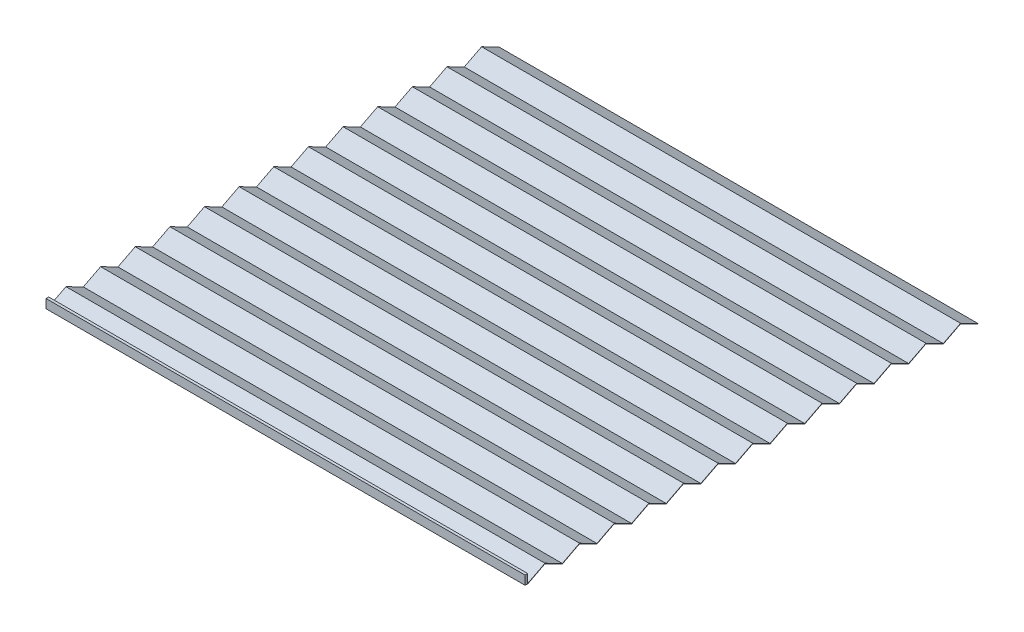
SolidWorks part; units mm, degrees
ref_plane "Front Plane" through (0, 0, 0) normal (0, 0, 1) x (1, 0, 0)
ref_plane "Top Plane" through (0, 0, 0) normal (0, 1, 0) x (1, 0, 0)
ref_plane "Right Plane" through (0, 0, 0) normal (1, 0, 0) x (0, 0, -1)
sketch "Sketch2" plane through (0, 0, 0) normal (0, 0, 1) x (1, 0, 0)
  line L1 (-270, 10) -> (270, 10)
  line L2 (-270, 10) -> (-270, 0)
  line L3 (-270, 0) -> (270, 0)
  line L4 (270, 10) -> (270, 0)
  point P4 (0, 0)
  dimension "D1" = 10
  dimension "D2" = 540
extrude "Boss-Extrude1" add sketch "Sketch2" along normal blind 3
sketch "Sketch3" plane through (270, 0, 0) normal (1, 0, 0) x (0, 0, -1)
  line L0 (0, 10) -> (507.5563, 10) construction
  line L1 (0, 0) -> (507.5563, 0) construction
  line L2 (507.5563, 10) -> (507.5563, 0) construction
  line L3 (0, 0) -> (19.5214, 10)
  line L4 (19.5214, 10) -> (39.0428, 0)
  line L5 (39.0428, 0) -> (58.5642, 10)
  line L6 (58.5642, 10) -> (78.0856, 0)
  line L7 (78.0856, 0) -> (97.607, 10)
  line L8 (97.607, 10) -> (117.1284, 0)
  line L9 (117.1284, 0) -> (136.6498, 10)
  line L10 (136.6498, 10) -> (156.1712, 0)
  line L11 (156.1712, 0) -> (175.6926, 10)
  line L12 (175.6926, 10) -> (195.214, 0)
  line L13 (195.214, 0) -> (214.7354, 10)
  line L14 (214.7354, 10) -> (234.2568, 0)
  line L15 (234.2568, 0) -> (253.7782, 10)
  line L16 (253.7782, 10) -> (273.2996, 0)
  line L17 (273.2996, 0) -> (292.821, 10)
  line L18 (292.821, 10) -> (312.3423, 0)
  line L20 (312.3423, 0) -> (331.8637, 10)
  line L21 (331.8637, 10) -> (351.3851, 0)
  line L22 (351.3851, 0) -> (370.9065, 10)
  line L23 (370.9065, 10) -> (390.4279, 0)
  line L24 (390.4279, 0) -> (409.9493, 10)
  line L25 (409.9493, 10) -> (429.4707, 0)
  line L26 (429.4707, 0) -> (448.9921, 10)
  line L27 (448.9921, 10) -> (468.5135, 0)
  line L28 (468.5135, 0) -> (488.0349, 10)
  line L29 (488.0349, 10) -> (507.5563, 0)
  line L30 (507.5563, 10) -> (507.5563, 0) construction
extrude "Extrude-Thin1" add sketch "Sketch3" against normal through all thin thin type mid plane wall 0.5
